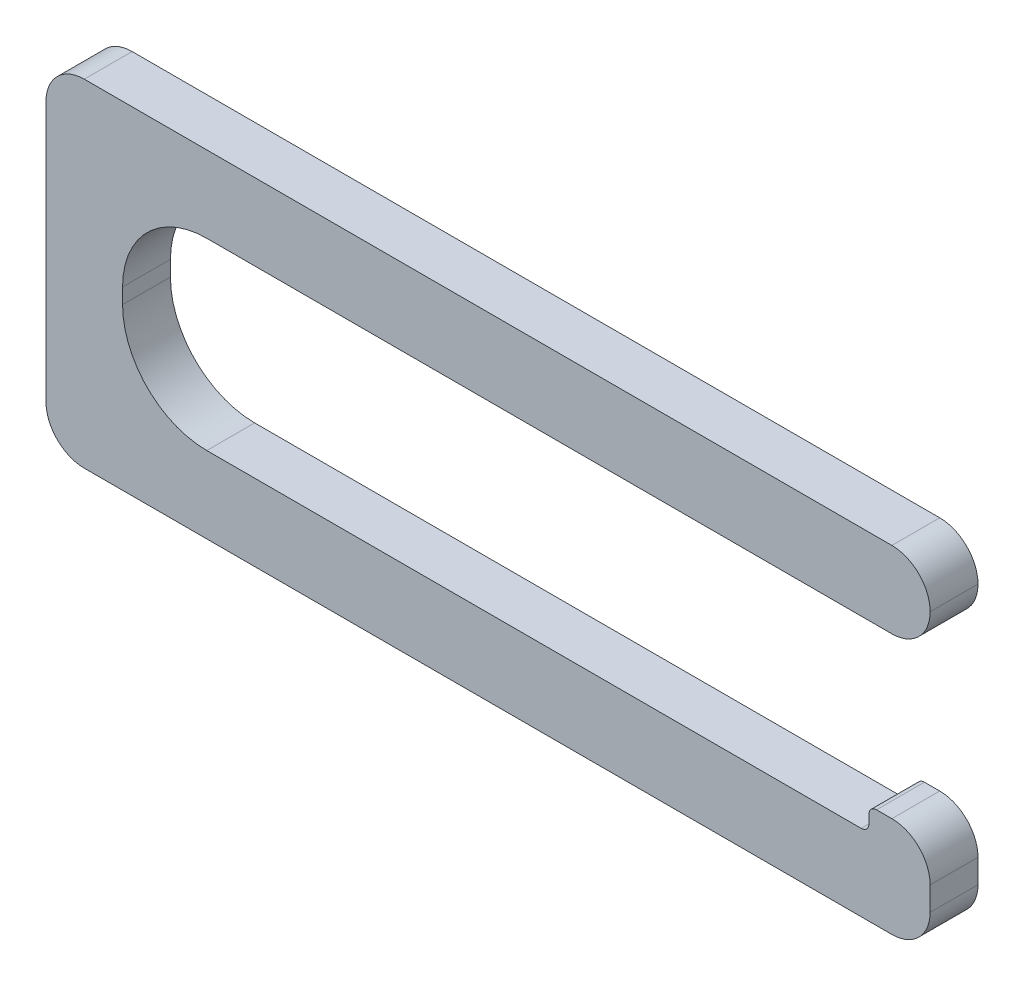
SolidWorks part; units mm, degrees
ref_plane "Front Plane" through (0, 0, 0) normal (0, 0, 1) x (1, 0, 0)
ref_plane "Top Plane" through (0, 0, 0) normal (0, 1, 0) x (1, 0, 0)
ref_plane "Right Plane" through (0, 0, 0) normal (1, 0, 0) x (0, 0, -1)
sketch "Sketch1" plane through (0, 0, 0) normal (0, 0, 1) x (1, 0, 0)
  line L0 (5.6519, 2.8486) -> (34.9792, 2.8486)
  line L1 (34.9792, 2.8486) -> (34.9792, 6.176)
  line L2 (32.9472, 5.3886) -> (8.1919, 5.3886)
  line L3 (8.1919, 5.3886) -> (8.1919, 11.4846)
  line L4 (8.1919, 11.4846) -> (34.9792, 11.4846)
  line L5 (34.9792, 11.4846) -> (34.9792, 14.0246)
  line L6 (34.9792, 14.0246) -> (5.6519, 14.0246)
  line L7 (5.6519, 14.0246) -> (5.6519, 2.8486)
  line L8 (16.7928, 5.3886) -> (32.9472, 5.3886) construction
  line L9 (34.9792, 6.176) -> (34.9792, 7.954) construction
  line L10 (32.9472, 5.3886) -> (32.9472, 6.176)
  line L11 (32.9472, 6.176) -> (34.9792, 6.176)
  line L13 (32.9472, 5.3886) -> (32.9472, 6.176) construction
  line L14 (16.7674, 6.176) -> (34.9792, 6.176) construction
  dimension "D1" = 2.54
  dimension "D2" = 2.54
  dimension "D3" = 2.54
  dimension "D4" = 6.096
extrude "Boss-Extrude1" add sketch "Sketch1" along normal blind 1.5875
fillet "Fillet1" radius 1.27 6 edges at (5.6519, 2.8486, 0.7937) (34.9792, 2.8486, 0.7937) (34.9792, 6.176, 0.7937) (5.6519, 14.0246, 0.7937) (34.9792, 11.4846, 0.7937) (34.9792, 14.0246, 0.7937)
fillet "Fillet2" radius 0.254 2 edges at (32.9472, 5.3886, 0.7937) (32.9472, 6.176, 0.7937)
fillet "Fillet3" radius 2.794 2 edges at (8.1919, 5.3886, 0.7937) (8.1919, 11.4846, 0.7937)
